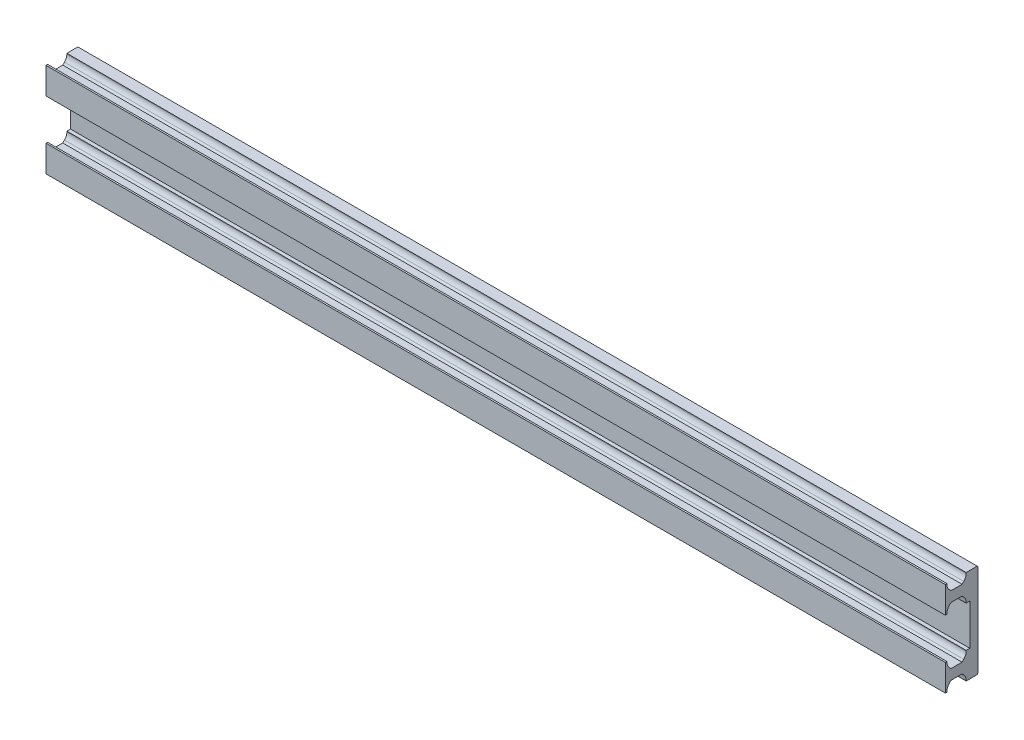
SolidWorks part; units mm, degrees
ref_plane "Front" through (0, 0, 0) normal (0, 0, 1) x (1, 0, 0)
ref_plane "Top" through (0, 0, 0) normal (0, 1, 0) x (1, 0, 0)
ref_plane "Right" through (0, 0, 0) normal (1, 0, 0) x (0, 0, -1)
sketch "Sketch1" plane through (0, 0, 0) normal (0, 0, 1) x (1, 0, 0)
  line L0 (110, -4.5) -> (110, 4.5) construction
  line L1 (-110, 11.5) -> (110, 11.5)
  line L2 (-110, 11.5) -> (-110, -11.5)
  line L3 (-110, -11.5) -> (110, -11.5)
  line L4 (110, 11.5) -> (110, -11.5)
  line L5 (-110, 11.5) -> (110, -11.5) construction
  line L6 (-110, -11.5) -> (110, 11.5) construction
  point P0 (0, 0)
  dimension "D1" = 7
extrude "Boss-Extrude1" add sketch "Sketch1" against normal blind 2
sketch "Sketch2" plane through (0, 0, 0) normal (0, 0, 1) x (1, 0, 0)
  line L0 (110, 11.5) -> (110, -11.5) construction
  line L1 (-110, 11.5) -> (110, 11.5)
  line L2 (-110, 11.5) -> (-110, 5)
  line L3 (-110, 5) -> (110, 5)
  line L4 (110, 11.5) -> (110, 5)
  line L5 (-110, -11.5) -> (-110, 11.5) construction
  line L6 (-110, -11.5) -> (110, -11.5)
  line L7 (-110, -11.5) -> (-110, -5)
  line L8 (-110, -5) -> (110, -5)
  line L9 (110, -11.5) -> (110, -5)
  line L11 (-110, 4.5) -> (110, 4.5) construction
  dimension "D1" = 0.5
extrude "Boss-Extrude2" add sketch "Sketch2" along normal offset from surface (6 mm away) 1
ref_plane "Center of Slots" through (0, 8.25, 0) normal (0, -1, 0) x (-1, 0, 0)
sketch "Sketch5" plane through (0, 0, 0) normal (1, 0, 0) x (0, 0, -1)
  line L16 (-1.9, 7) -> (-4.6, 7)
  line L17 (-1.9, 7) -> (-4.6, 7)
  line L18 (-4.6, 7) -> (-5.0142, 6.5858)
  line L19 (-4.6, 7) -> (-5.0142, 6.5858)
  line L20 (-5.6, 5.1716) -> (-5.6, 4.3284)
  line L21 (-5.6, 5.1716) -> (-5.6, 4.3284)
  line L22 (-5.0142, 2.9142) -> (-4.6, 2.5)
  line L23 (-5.0142, 2.9142) -> (-4.6, 2.5)
  line L24 (-4.6, 2.5) -> (-1.9, 2.5)
  line L25 (-4.6, 2.5) -> (-1.9, 2.5)
  line L26 (-1.9, 2.5) -> (-1.4858, 2.9142)
  line L27 (-1.9, 2.5) -> (-1.4858, 2.9142)
  line L28 (-0.9, 4.3284) -> (-0.9, 5.1716)
  line L29 (-0.9, 4.3284) -> (-0.9, 5.1716)
  line L30 (-1.4858, 6.5858) -> (-1.9, 7)
  line L31 (-1.4858, 6.5858) -> (-1.9, 7)
  arc A12 (-5.0142, 6.5858) -> (-5.6, 5.1716) centre (-3.6, 5.1716) ccw
  arc A13 (-5.0142, 6.5858) -> (-5.6, 5.1716) centre (-3.6, 5.1716) ccw
  arc A14 (-5.6, 4.3284) -> (-5.0142, 2.9142) centre (-3.6, 4.3284) ccw
  arc A15 (-5.6, 4.3284) -> (-5.0142, 2.9142) centre (-3.6, 4.3284) ccw
  arc A16 (-1.4858, 2.9142) -> (-0.9, 4.3284) centre (-2.9, 4.3284) ccw
  arc A17 (-1.4858, 2.9142) -> (-0.9, 4.3284) centre (-2.9, 4.3284) ccw
  arc A18 (-0.9, 5.1716) -> (-1.4858, 6.5858) centre (-2.9, 5.1716) ccw
  arc A19 (-0.9, 5.1716) -> (-1.4858, 6.5858) centre (-2.9, 5.1716) ccw
  dimension "D1" = 0
extrude "Middle Slot" cut sketch "Sketch5" against normal through all both and the other way through all
mirror "Middle Slots" about plane through (0, 0, 0) normal (0, 1, 0) of "Middle Slot"
sketch "Sketch7" plane through (0, 0, 0) normal (1, 0, 0) x (0, 0, -1)
  line L8 (-1.875, 13.975) -> (-4.625, 13.975)
  line L9 (-4.625, 13.975) -> (-5.0142, 13.5858)
  line L10 (-5.6, 12.1716) -> (-5.6, 11.3284)
  line L11 (-5.0142, 9.9142) -> (-4.6, 9.5)
  line L12 (-4.6, 9.5) -> (-1.9, 9.5)
  line L13 (-1.9, 9.5) -> (-1.4858, 9.9142)
  line L14 (-0.9, 11.3284) -> (-0.9, 12.1716)
  line L15 (-1.4858, 13.5858) -> (-1.875, 13.975)
  line L16 (-1.875, 13.975) -> (-4.625, 13.975)
  line L17 (-4.625, 13.975) -> (-5.0142, 13.5858)
  line L18 (-5.6, 12.1716) -> (-5.6, 11.3284)
  line L19 (-5.0142, 9.9142) -> (-4.6, 9.5)
  line L20 (-4.6, 9.5) -> (-1.9, 9.5)
  line L21 (-1.9, 9.5) -> (-1.4858, 9.9142)
  line L22 (-0.9, 11.3284) -> (-0.9, 12.1716)
  line L23 (-1.4858, 13.5858) -> (-1.875, 13.975)
  arc A4 (-5.0142, 13.5858) -> (-5.6, 12.1716) centre (-3.6, 12.1716) ccw
  arc A5 (-5.6, 11.3284) -> (-5.0142, 9.9142) centre (-3.6, 11.3284) ccw
  arc A6 (-1.4858, 9.9142) -> (-0.9, 11.3284) centre (-2.9, 11.3284) ccw
  arc A7 (-0.9, 12.1716) -> (-1.4858, 13.5858) centre (-2.9, 12.1716) ccw
  arc A8 (-5.0142, 13.5858) -> (-5.6, 12.1716) centre (-3.6, 12.1716) ccw
  arc A9 (-5.6, 11.3284) -> (-5.0142, 9.9142) centre (-3.6, 11.3284) ccw
  arc A10 (-1.4858, 9.9142) -> (-0.9, 11.3284) centre (-2.9, 11.3284) ccw
  arc A11 (-0.9, 12.1716) -> (-1.4858, 13.5858) centre (-2.9, 12.1716) ccw
  dimension "D1" = 0
extrude "Top Slot" cut sketch "Sketch7" against normal through all both and the other way through all
mirror "Top Slots" about plane through (0, 0, 0) normal (0, 1, 0) of "Top Slot"
chamfer "Deburs" distance 0.2 angle 45 2 edges at (0, -11.5, -2) (0, 11.5, -2)
